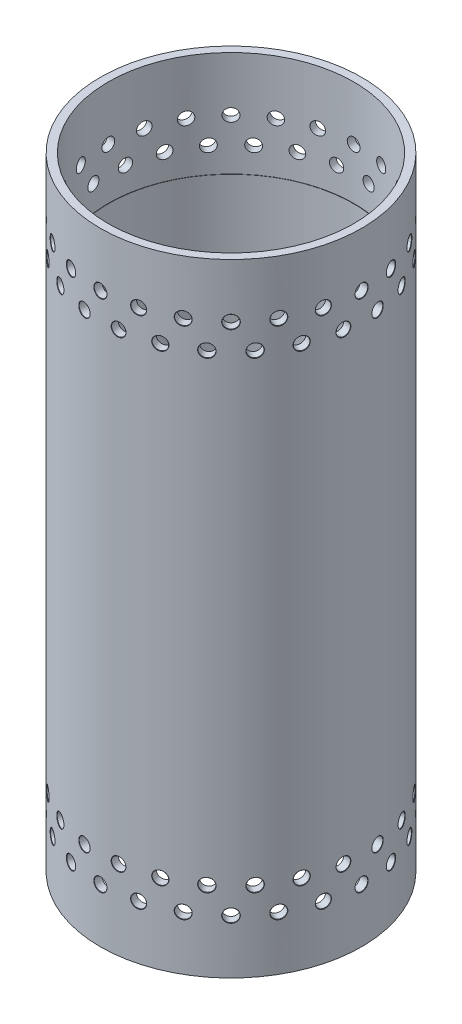
SolidWorks part; units mm, degrees
material "AW-6082-T6 (PA4)"
ref_plane "Płaszczyzna przednia" through (0, 0, 0) normal (0, 0, 1) x (1, 0, 0)
ref_plane "Płaszczyzna górna" through (0, 0, 0) normal (0, 1, 0) x (1, 0, 0)
ref_plane "Płaszczyzna prawa" through (0, 0, 0) normal (1, 0, 0) x (0, 0, -1)
sketch "Szkic1" plane through (0, 0, 0) normal (0, 1, 0) x (1, 0, 0)
  circle A0 centre (0, 0) radius 90
  circle A1 centre (0, 0) radius 81.5
  dimension "D1" = 8.5
  dimension "D2" = 180
  dimension "D3" = 163
extrude "Dodanie-wyciągnięcie1" add sketch "Szkic1" along normal blind 414
sketch "Szkic2" plane through (0, 414, 0) normal (0, 1, 0) x (1, 0, 0)
  circle A0 centre (0, 0) radius 87
  circle A1 centre (0, 0) radius 90 construction
  circle A2 centre (0, 0) radius 90
  dimension "D1" = 174
extrude "Wytnij-wyciągnięcie1" cut sketch "Szkic2" against normal through all
sketch "Szkic3" plane through (0, 414, 0) normal (0, 1, 0) x (1, 0, 0)
  circle A0 centre (0, 0) radius 81.7
  circle A1 centre (0, 0) radius 81.5 construction
  circle A2 centre (0, 0) radius 81.5
  dimension "D1" = 0.2
extrude "Wytnij-wyciągnięcie2" cut sketch "Szkic3" against normal blind 70
ref_plane "Płaszczyzna1" through (0, 0, 87) normal (0, 0, 1) x (1, 0, 0)
ref_plane "Płaszczyzna2" through (11.3558, 0, 86.2557) normal (0.1305, 0, 0.9914) x (0, 1, 0)
hole_wizard "Otwór Ø8.5 (8.5)1" positions "Szkic5" profile "Szkic6" hole size "Ø8.5" standard "DIN" end condition up to next
sketch "Szkic5" plane through (0, 0, 87) normal (0, 0, 1) x (1, 0, 0)
  line L0 (87, 414) -> (-87, 414) construction
  line L1 (87, 0) -> (87, 414) construction
  line L2 (-87, 414) -> (-87, 0) construction
  line L3 (87, 0) -> (87, 414)
  line L4 (-87, 414) -> (-87, 0)
  line L5 (0, 869.2816) -> (0, 760.9563) construction
  point P0 (0, 378)
  dimension "D1" = 36
sketch "Szkic6" plane through (0, 378, 87) normal (1, 0, 0) x (0, -1, 0)
  line L0 (0, 0) -> (0, 5.3)
  line L1 (0, 5.3) -> (4.25, 5.3)
  line L2 (4.25, 5.3) -> (4.25, 0.25)
  line L3 (4.25, 0.25) -> (4.5, 0)
  line L5 (4.5, 0) -> (0, 0)
  line L6 (-4.25, 0.25) -> (-4.5, 0) construction
  line L11 (0, -6.35) -> (0, 107.95) construction
  dimension "Średnica otworu na wylot" = 8.5
  dimension "Głębokość otworu na wylot" = 5.3
  dimension "Średnica zewnętrznego pogłębienia stożkowego" = 9
  dimension "Kąt zewnętrznego pogłębienia stożkowego" = 90
hole_wizard "Otwór Ø8.5 (8.5)2" positions "Szkic7" profile "Szkic8" hole size "Ø8.5" standard "BSI" end condition up to next
sketch "Szkic7" plane through (11.3558, 0, 86.2557) normal (0.1305, 0, 0.9914) x (0, 1, 0)
  line L0 (414, -87) -> (414, 87) construction
  line L1 (0, -87) -> (414, -87) construction
  line L2 (414, 87) -> (0, 87) construction
  line L3 (0, -87) -> (414, -87)
  line L4 (414, 87) -> (0, 87)
  line L5 (862.9512, 0) -> (744.0524, 0) construction
  ellipse E0 centre (378, 11.3231) end of major axis (382.25, 11.3231) minor radius 4.2136 construction
  point P0 (361, 0)
  dimension "D1" = 53
  dimension "D2" = 20.4258
sketch "Szkic8" plane through (11.3558, 361, 86.2557) normal (0, 1, 0) x (0.9914, 0, -0.1305)
  line L0 (0, 0) -> (0, 5.3)
  line L1 (0, 5.3) -> (4.25, 5.3)
  line L2 (4.25, 5.3) -> (4.25, 0.25)
  line L3 (4.25, 0.25) -> (4.5, 0)
  line L5 (4.5, 0) -> (0, 0)
  line L6 (-4.25, 0.25) -> (-4.5, 0) construction
  line L11 (0, -6.35) -> (0, 107.95) construction
  dimension "Średnica otworu na wylot" = 8.5
  dimension "Głębokość otworu na wylot" = 5.3
  dimension "Średnica zewnętrznego pogłębienia stożkowego" = 9
  dimension "Kąt zewnętrznego pogłębienia stożkowego" = 90
pattern_circular "Szyk kołowy1" count 24 over 360 about axis through (0, 0, 0) along (0, 1, 0) of "Otwór Ø8.5 (8.5)1", "Otwór Ø8.5 (8.5)2" reverse direction yes
ref_plane "Płaszczyzna3" through (0, 207, 0) normal (0, 1, 0) x (1, 0, 0)
mirror "Lustro1" about plane through (0, 207, 0) normal (0, 1, 0) of "Otwór Ø8.5 (8.5)2", "Otwór Ø8.5 (8.5)1", "Szyk kołowy1", "Wytnij-wyciągnięcie2"
